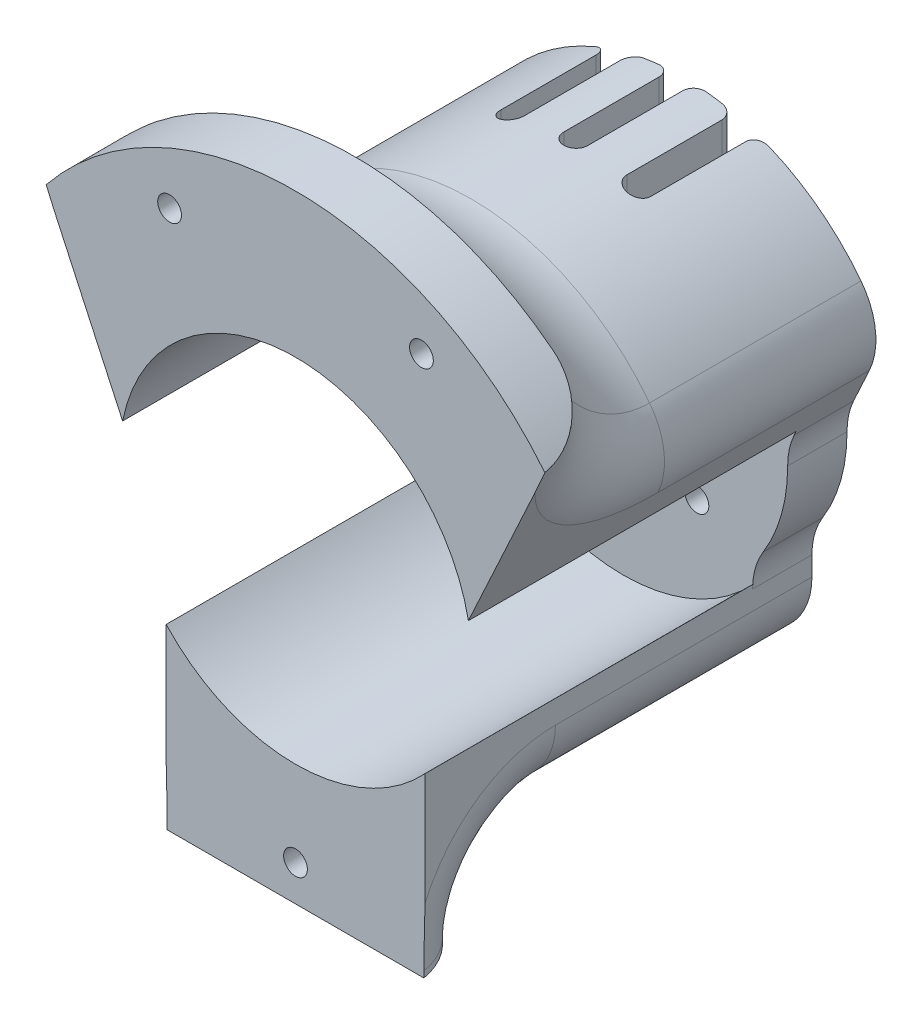
SolidWorks part; units mm, degrees
ref_plane "Front Plane" through (0, 0, 0) normal (0, 0, 1) x (1, 0, 0)
ref_plane "Top Plane" through (0, 0, 0) normal (0, 1, 0) x (1, 0, 0)
ref_plane "Right Plane" through (0, 0, 0) normal (1, 0, 0) x (0, 0, -1)
sketch "Sketch1" plane through (0, 0, 0) normal (0, 0, 1) x (1, 0, 0)
  line L1 (6.2099, -6.2099) -> (-6.2099, -6.2099) construction
  line L2 (6.2099, -6.2099) -> (6.2099, 6.2099) construction
  line L3 (6.2099, 6.2099) -> (-6.2099, 6.2099) construction
  line L4 (-6.2099, -6.2099) -> (-6.2099, 6.2099) construction
  line L5 (6.2099, -6.2099) -> (-6.2099, 6.2099) construction
  line L6 (6.2099, 6.2099) -> (-6.2099, -6.2099) construction
  circle A0 centre (0, 0) radius 13.85
  circle A1 centre (-6.2099, 6.2099) radius 1
  circle A2 centre (-6.2099, -6.2099) radius 1
  circle A3 centre (6.2099, -6.2099) radius 1
  circle A4 centre (6.2099, 6.2099) radius 1
  circle A5 centre (0, 0) radius 2.8
  dimension "D1" = 27.7
  dimension "D3" = 2
  dimension "D4" = 5.6
  dimension "D2" = 12.4197
extrude "Boss-Extrude1" add sketch "Sketch1" along normal blind 5
sketch "Sketch3" plane through (0, 0, 0) normal (0, 0, -1) x (-1, 0, 0)
  line L0 (-6.2099, -6.2099) -> (-6.2099, 6.2099) construction
ref_axis "Axis1" through (6.2099, 17.0042, 0) along (0, -1, 0)
sketch "Sketch4" plane through (0, 0, 0) normal (0, 0, -1) x (-1, 0, 0)
  line L2 (11.8156, -3.0368) -> (22.6956, 20.5161) construction
  line L3 (-22.6956, 20.5161) -> (-11.8156, -3.0368) construction
  line L4 (13.7939, 1.2457) -> (17.0714, 8.3408)
  line L5 (-17.0714, 8.3408) -> (-13.7939, 1.2457)
  arc A1 (17.0714, 8.3408) -> (-17.0714, 8.3408) centre (0, 0) ccw
  circle A2 centre (0, 0) radius 13.85 construction
  arc A3 (13.7939, 1.2457) -> (-13.7939, 1.2457) centre (0, 0) ccw
  dimension "D1" = 38
extrude "Boss-Extrude2" add sketch "Sketch4" against normal up to surface (32.6 mm away)
sketch "Sketch5" plane through (0, 0, 32.6) normal (0, 0, -1) x (-1, 0, 0)
  line L0 (10.6066, 20.3934) -> (0, 0) construction
  line L1 (10.6066, 20.3934) -> (12.4462, 23.9304) construction
  line L2 (10.6066, 20.3934) -> (4.3808, 23.6314) construction
  line L3 (4.3808, 23.6314) -> (8.767, 16.8564) construction
  line L4 (4.3808, 23.6314) -> (12.4462, 23.9304) construction
  line L5 (-22.6956, 20.5161) -> (-11.8156, -3.0368) construction
  line L6 (-21.0243, 16.8982) -> (-17.0714, 8.3408)
  line L7 (11.8156, -3.0368) -> (22.6956, 20.5161) construction
  line L8 (17.0714, 8.3408) -> (21.0243, 16.8982)
  arc A0 (21.0243, 16.8982) -> (-21.0243, 16.8982) centre (0, 0) ccw
  arc A1 (17.0714, 8.3408) -> (-17.0714, 8.3408) centre (0, 0) ccw construction
  arc A2 (17.0714, 8.3408) -> (-17.0714, 8.3408) centre (0, 0) ccw
  circle A3 centre (-10.6066, 20.3934) radius 1 construction
  circle A4 centre (10.6066, 20.3934) radius 1 construction
  circle A5 centre (-10.6066, 20.3934) radius 1
  circle A6 centre (10.6066, 20.3934) radius 1
extrude "Boss-Extrude3" add sketch "Sketch5" along normal blind 5
sketch "Sketch6" plane through (0, 0, 27.6) normal (0, 0, -1) x (-1, 0, 0)
  circle A0 centre (-10.6066, 20.3934) radius 2
  circle A1 centre (10.6066, 20.3934) radius 2
  dimension "D1" = 4
extrude "Cut-Extrude1" cut sketch "Sketch6" against normal blind 3
fillet "Fillet1" radius 10 1 edges at (0, 19, 27.6)
sketch "Sketch7" plane through (0, 0, 0) normal (0, 0, -1) x (-1, 0, 0)
  line L0 (10.8939, -25.0323) -> (10.8939, -7.2303) construction
  line L1 (-10.8939, -7.2303) -> (-10.8939, -25.0323) construction
  line L2 (10.8939, -15.5667) -> (10.8939, -8.5526)
  line L3 (-10.8939, -8.5526) -> (-10.8939, -15.5667)
  arc A0 (-10.8939, -15.5667) -> (10.8939, -15.5667) centre (0, 0) ccw
  arc A1 (17.0714, 8.3408) -> (-17.0714, 8.3408) centre (0, 0) ccw construction
  arc A2 (-13.7939, 1.2457) -> (13.7939, 1.2457) centre (0, 0) ccw construction
  arc A3 (-10.8939, -8.5526) -> (10.8939, -8.5526) centre (0, 0) ccw
extrude "Boss-Extrude4" add sketch "Sketch7" against normal up to surface (32.6 mm away)
sketch "Sketch8" plane through (0, 0, 32.6) normal (0, 0, -1) x (-1, 0, 0)
  line L0 (-10.8939, -15.5667) -> (-10.8939, -25.0323)
  line L1 (-10.8939, -25.0323) -> (10.8939, -25.0323)
  line L2 (10.8939, -25.0323) -> (10.8939, -15.5667)
  line L3 (0, -19) -> (0, -25.0323) construction
  line L4 (0, -25.0323) -> (0, -22.0161) construction
  arc A0 (-10.8939, -15.5667) -> (10.8939, -15.5667) centre (0, 0) ccw construction
  arc A1 (-10.8939, -15.5667) -> (10.8939, -15.5667) centre (0, 0) ccw
  circle A2 centre (0, -22.0161) radius 1
  point P13 (0, -22.0161)
  point P15 (0, -22.0161)
  point P16 (0.0562, -22.0161)
  dimension "D1" = 2
extrude "Boss-Extrude5" add sketch "Sketch8" along normal blind 5
sketch "Sketch9" plane through (0, 0, 27.6) normal (0, 0, -1) x (-1, 0, 0)
  circle A0 centre (0, -22.0161) radius 2
  dimension "D1" = 4
extrude "Cut-Extrude2" cut sketch "Sketch9" against normal blind 3
fillet "Fillet2" radius 6 1 edges at (0, -19, 27.6)
fillet "Fillet3" radius 6 14 edges at (17.8903, 10.1136, 23.1569) (10.8939, -23.7669, 27.6) (10.8939, -17.7797, 25.935) (-10.8939, -23.7669, 27.6) (-10.8939, -16.7498, 24.8875) (-17.9693, 10.2848, 23.3917) (17.0714, 8.3408, 8.9037) (10.8939, -15.5667, 10.8) (-10.8939, -15.5667, 10.8) (-17.0714, 8.3408, 8.9037) (-10.8939, -8.5526, 2.5) (-13.7939, 1.2457, 2.5) (10.8939, -8.5526, 2.5) (13.7939, 1.2457, 2.5)
sketch "Sketch10" plane through (0, 0, 0) normal (0, 0, -1) x (-1, 0, 0)
  line L0 (-6.3119, 11.0786) -> (0, 0) construction
  line L3 (-6.3119, 11.0786) -> (-4.3119, 11.0786)
  line L4 (-4.3119, 17.9209) -> (-4.3119, 11.0786)
  line L5 (-1, 19.4264) -> (1, 19.4264)
  line L6 (-1, 19.4264) -> (-1, 11.0786)
  line L7 (-1, 11.0786) -> (1, 11.0786)
  line L8 (1, 19.4264) -> (1, 11.0786)
  line L11 (4.3119, 11.0786) -> (6.3119, 11.0786)
  line L12 (6.3119, 18.5042) -> (6.3119, 11.0786)
  line L13 (0, 0) -> (6.3119, 11.0786) construction
  line L14 (0, 0) -> (0, 38.0039) construction
  line L15 (-1, 19.4264) -> (0, 11.0786) construction
  line L16 (0, 11.0786) -> (1, 19.4264) construction
  line L17 (-6.3119, 11.0786) -> (-6.3119, 19.4264)
  line L18 (-6.3119, 19.4264) -> (-4.3119, 19.4264)
  line L19 (-4.3119, 19.4264) -> (-4.3119, 17.9209)
  line L20 (4.3119, 11.0786) -> (4.3119, 19.4264)
  line L21 (4.3119, 19.4264) -> (6.3119, 19.4264)
  line L22 (6.3119, 19.4264) -> (6.3119, 18.5042)
extrude "Cut-Extrude3" cut sketch "Sketch10" against normal blind 10
fillet "Fillet4" radius 1 12 edges at (-6.3119, 14.4998, 0) (6.3119, 14.4998, 0) (4.3119, 14.7914, 0) (1, 15.0261, 0) (-1, 15.0261, 0) (-4.3119, 14.7914, 0) (-6.3119, 15.1245, 10) (-4.3119, 15.833, 10) (-1, 16.3938, 10) (1, 16.3938, 10) (6.3119, 15.1245, 10) (4.3119, 15.833, 10)
sketch "Sketch11" plane through (0, 0, 32.6) normal (0, 0, 1) x (1, 0, 0)
  circle A0 centre (0, 0) radius 14.85
  arc A1 (-6.3119, 12.3281) -> (-13.7939, 1.2457) centre (0, 0) ccw construction
  dimension "D1" = 1
extrude "Cut-Extrude4" cut sketch "Sketch11" against normal up to surface (27.6 mm away) up to face at (0, 4.0417, 5)
